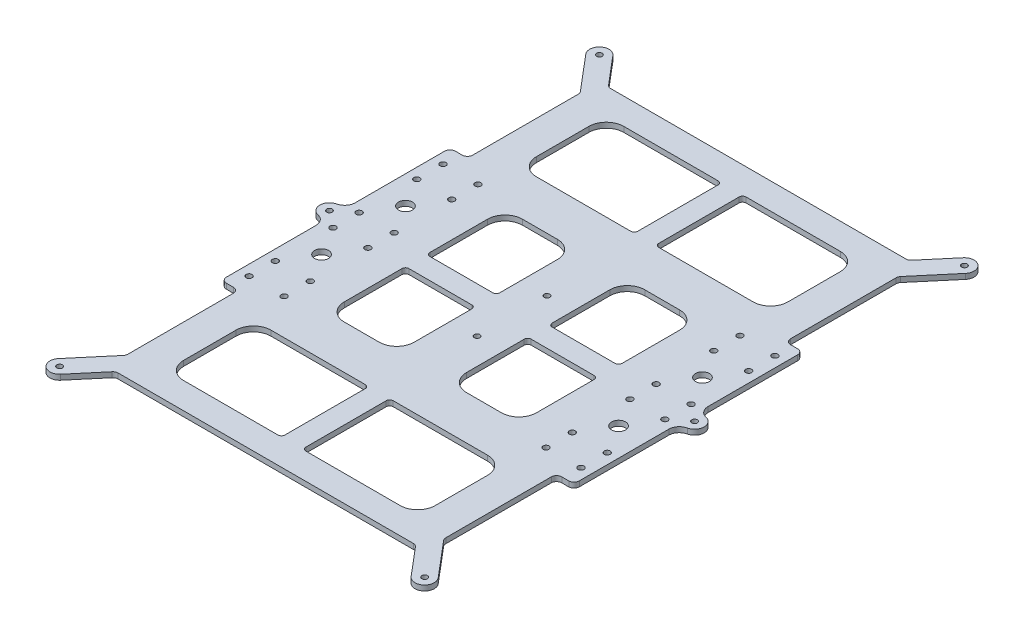
SolidWorks part; units mm, degrees
ref_plane "Alzado" through (0, 0, 0) normal (0, 0, 1) x (1, 0, 0)
ref_plane "Planta" through (0, 0, 0) normal (0, 1, 0) x (1, 0, 0)
ref_plane "Vista lateral" through (0, 0, 0) normal (1, 0, 0) x (0, 0, -1)
sketch "Croquis1" plane through (0, 0, 0) normal (0, 1, 0) x (1, 0, 0)
  line L0 (110, 320) -> (110, 0) construction
  line L1 (0, 0) -> (220, 0)
  line L2 (0, 0) -> (0, 320)
  line L3 (0, 320) -> (220, 320)
  line L4 (220, 0) -> (220, 320)
  line L5 (0, 160) -> (220, 160) construction
  line L6 (19, 320) -> (19, 0) construction
  line L7 (31, 320) -> (31, 0) construction
  line L8 (189, 320) -> (189, 0) construction
  line L9 (201, 320) -> (201, 0) construction
  line L10 (195, 320) -> (195, 0) construction
  line L11 (25, 320) -> (25, 0) construction
  line L12 (5.5, 314.5) -> (5.5, 160) construction
  circle A0 centre (185, 167.5) radius 1.7
  circle A1 centre (205, 167.5) radius 1.7
  circle A4 centre (185, 152.5) radius 1.7
  circle A5 centre (205, 152.5) radius 1.7
  circle A7 centre (35, 215.5) radius 1.7
  circle A8 centre (35, 200.5) radius 1.7
  circle A10 centre (35, 119.5) radius 1.7
  circle A13 centre (35, 104.5) radius 1.7
  circle A14 centre (5.5, 314.5) radius 1.6
  circle A15 centre (214.5, 314.5) radius 1.6
  circle A16 centre (214.5, 5.5) radius 1.6
  circle A17 centre (5.5, 5.5) radius 1.6
  circle A18 centre (15, 200.5) radius 1.7
  circle A19 centre (15, 215.5) radius 1.7
  circle A20 centre (15, 104.5) radius 1.7
  circle A21 centre (15, 119.5) radius 1.7
  circle A22 centre (110, 180) radius 1.6
  circle A23 centre (110, 140) radius 1.6
  circle A24 centre (185, 104.5) radius 1.7
  circle A25 centre (205, 104.5) radius 1.7
  circle A26 centre (205, 119.5) radius 1.7
  circle A27 centre (185, 119.5) radius 1.7
  circle A28 centre (185, 200.5) radius 1.7
  circle A29 centre (185, 215.5) radius 1.7
  circle A30 centre (205, 200.5) radius 1.7
  circle A31 centre (205, 215.5) radius 1.7
  circle A32 centre (5.5, 160) radius 1.6
  circle A33 centre (35, 152.5) radius 1.7
  circle A34 centre (15, 152.5) radius 1.7
  circle A35 centre (15, 167.5) radius 1.7
  circle A36 centre (35, 167.5) radius 1.7
  circle A37 centre (214.5, 160) radius 1.6
  circle A38 centre (25, 136) radius 4
  circle A39 centre (25, 184) radius 4
  circle A40 centre (195, 136) radius 4
  circle A41 centre (195, 184) radius 4
  dimension "D8" = 3.4
  dimension "D13" = 6
  dimension "D14" = 3.4
  dimension "D17" = 3.2
  dimension "D23" = 3.2
  dimension "D18" = 20
  dimension "D19" = 8
  dimension "D1" = 320
  dimension "D2" = 220
  dimension "D3" = 12
  dimension "D4" = 12
  dimension "D5" = 158
  dimension "D6" = 19
  dimension "D7" = 6
  dimension "D9" = 20
  dimension "D10" = 10
  dimension "D11" = 7.5
  dimension "D12" = 7.5
  dimension "D15" = 10
  dimension "D16" = 15
  dimension "D20" = 10
  dimension "D21" = 104.5
  dimension "D22" = 16.5
  dimension "D24" = 5.5
  dimension "D25" = 5.5
extrude "Saliente-Extruir1" add sketch "Croquis1" along normal blind 3
sketch "Croquis2" plane through (0, 3, 0) normal (0, 1, 0) x (1, 0, 0)
  line L0 (220, 160) -> (0, 160) construction
  line L2 (9, 9) -> (211, 9) construction
  line L3 (220, 0) -> (220, 320) construction
  line L4 (9, 148.775) -> (9, 94.5)
  line L5 (110, 320) -> (110, 0) construction
  line L6 (220, 320) -> (0, 320) construction
  line L7 (0, 0) -> (220, 0) construction
  line L8 (9, 9) -> (211, 9)
  line L9 (211, 9) -> (211, 311)
  line L10 (211, 311) -> (9, 311)
  line L11 (9, 311) -> (9, 9)
  line L15 (9, 225.5) -> (9, 171.225)
  line L16 (9, 225.5) -> (19, 225.5)
  line L18 (19, 94.5) -> (9, 94.5)
  line L19 (19, 94.5) -> (19, 30)
  line L20 (24.1066, 19) -> (195.8934, 19)
  line L21 (210.2988, 1.9504) -> (195.8934, 19)
  line L22 (1.2988, 9.0496) -> (19, 30)
  line L23 (9.7012, 1.9504) -> (24.1066, 19)
  line L24 (9, 148.775) -> (9, 9) construction
  line L25 (19, 148.775) -> (19, 19) construction
  line L26 (19, 19) -> (201, 19) construction
  line L27 (211, 9) -> (211, 311) construction
  line L28 (19, 225.5) -> (19, 290)
  line L29 (24.1066, 301) -> (195.8934, 301)
  line L30 (1.2988, 310.9504) -> (19, 290)
  line L31 (9.7012, 318.0496) -> (24.1066, 301)
  line L32 (0, 320) -> (0, 0) construction
  line L33 (218.7012, 9.0496) -> (201, 30)
  line L34 (201, 19) -> (201, 311) construction
  line L35 (201, 94.5) -> (201, 30)
  line L36 (201, 94.5) -> (211, 94.5)
  line L37 (211, 148.775) -> (211, 94.5)
  line L38 (211, 225.5) -> (211, 171.225)
  line L39 (211, 225.5) -> (201, 225.5)
  line L40 (201, 225.5) -> (201, 290)
  line L41 (218.7012, 310.9504) -> (201, 290)
  line L42 (210.2988, 318.0496) -> (195.8934, 301)
  line L43 (182, 276) -> (182, 246)
  line L44 (102, 286) -> (48, 286)
  line L46 (102, 236) -> (48, 236)
  line L47 (38, 276) -> (38, 246)
  line L48 (118, 236) -> (172, 236)
  line L52 (104, 284) -> (104, 238)
  line L53 (116, 284) -> (116, 238)
  line L54 (118, 286) -> (172, 286)
  line L55 (102, 84) -> (48, 84)
  line L56 (38, 44) -> (38, 74)
  line L57 (102, 34) -> (48, 34)
  line L58 (104, 36) -> (104, 82)
  line L59 (116, 36) -> (116, 82)
  line L60 (118, 34) -> (172, 34)
  line L61 (182, 44) -> (182, 74)
  line L62 (118, 84) -> (172, 84)
  line L63 (55, 152) -> (55, 119)
  line L64 (93, 166) -> (57, 166)
  line L65 (95, 168) -> (95, 201)
  line L66 (85, 211) -> (65, 211)
  line L67 (55, 168) -> (55, 201)
  line L68 (85, 109) -> (65, 109)
  line L69 (95, 152) -> (95, 119)
  line L70 (93, 154) -> (57, 154)
  line L71 (135, 109) -> (155, 109)
  line L72 (165, 152) -> (165, 119)
  line L73 (125, 152) -> (125, 119)
  line L74 (127, 154) -> (163, 154)
  line L75 (127, 166) -> (163, 166)
  line L76 (165, 168) -> (165, 201)
  line L77 (135, 211) -> (155, 211)
  line L78 (125, 168) -> (125, 201)
  arc A2 (1.2988, 9.0496) -> (9.7012, 1.9504) centre (5.5, 5.5) ccw
  arc A3 (4.3043, 165.3685) -> (4.3043, 154.6315) centre (5.5, 160) ccw
  arc A4 (9, 148.775) -> (4.3043, 154.6315) centre (3, 148.775) ccw
  arc A5 (9, 171.225) -> (4.3043, 165.3685) centre (3, 171.225) cw
  circle A6 centre (35, 215.5) radius 1.7 construction
  circle A7 centre (35, 104.5) radius 1.7 construction
  arc A8 (48, 236) -> (38, 246) centre (48, 246) cw
  arc A10 (1.2988, 310.9504) -> (9.7012, 318.0496) centre (5.5, 314.5) cw
  arc A11 (218.7012, 9.0496) -> (210.2988, 1.9504) centre (214.5, 5.5) cw
  arc A12 (211, 148.775) -> (215.6957, 154.6315) centre (217, 148.775) cw
  arc A13 (215.6957, 165.3685) -> (215.6957, 154.6315) centre (214.5, 160) cw
  arc A14 (211, 171.225) -> (215.6957, 165.3685) centre (217, 171.225) ccw
  arc A15 (218.7012, 310.9504) -> (210.2988, 318.0496) centre (214.5, 314.5) ccw
  arc A16 (48, 286) -> (38, 276) centre (48, 276) ccw
  arc A17 (172, 236) -> (182, 246) centre (172, 246) ccw
  arc A18 (172, 286) -> (182, 276) centre (172, 276) cw
  arc A19 (48, 84) -> (38, 74) centre (48, 74) ccw
  arc A20 (48, 34) -> (38, 44) centre (48, 44) cw
  arc A21 (172, 34) -> (182, 44) centre (172, 44) ccw
  arc A22 (172, 84) -> (182, 74) centre (172, 74) cw
  arc A23 (102, 236) -> (104, 238) centre (102, 238) ccw
  arc A24 (102, 286) -> (104, 284) centre (102, 284) cw
  arc A25 (116, 284) -> (118, 286) centre (118, 284) cw
  arc A26 (118, 236) -> (116, 238) centre (118, 238) cw
  arc A27 (116, 82) -> (118, 84) centre (118, 82) cw
  arc A28 (116, 36) -> (118, 34) centre (118, 36) ccw
  arc A29 (102, 34) -> (104, 36) centre (102, 36) ccw
  arc A30 (102, 84) -> (104, 82) centre (102, 82) cw
  arc A31 (95, 201) -> (85, 211) centre (85, 201) ccw
  arc A32 (65, 211) -> (55, 201) centre (65, 201) ccw
  arc A33 (65, 109) -> (55, 119) centre (65, 119) cw
  arc A34 (95, 119) -> (85, 109) centre (85, 119) cw
  arc A35 (155, 109) -> (165, 119) centre (155, 119) ccw
  arc A36 (125, 119) -> (135, 109) centre (135, 119) ccw
  arc A37 (155, 211) -> (165, 201) centre (155, 201) cw
  arc A38 (125, 201) -> (135, 211) centre (135, 201) cw
  arc A39 (127, 166) -> (125, 168) centre (127, 168) cw
  arc A40 (163, 166) -> (165, 168) centre (163, 168) ccw
  arc A41 (165, 152) -> (163, 154) centre (163, 152) ccw
  arc A42 (125, 152) -> (127, 154) centre (127, 152) cw
  arc A43 (55, 152) -> (57, 154) centre (57, 152) cw
  arc A44 (95, 152) -> (93, 154) centre (93, 152) ccw
  arc A45 (93, 166) -> (95, 168) centre (93, 168) ccw
  arc A46 (57, 166) -> (55, 168) centre (57, 168) cw
  point P28 (110, 19)
  point P71 (110, 301)
  point P76 (38, 236)
  point P79 (38, 286)
  point P106 (104, 236)
  point P109 (104, 286)
  point P112 (116, 286)
  point P115 (116, 236)
  point P118 (116, 84)
  point P121 (116, 34)
  point P124 (104, 34)
  point P127 (104, 84)
  point P137 (95, 211)
  point P140 (55, 211)
  point P167 (125, 166)
  point P170 (165, 166)
  point P173 (165, 154)
  point P176 (125, 154)
  point P179 (55, 154)
  point P182 (95, 154)
  point P185 (95, 166)
  point P188 (55, 166)
  dimension "D2" = 11
  dimension "D3" = 11
  dimension "D4" = 6
  dimension "D5" = 10
  dimension "D6" = 10
  dimension "D7" = 50
  dimension "D12" = 10
  dimension "D14" = 2
  dimension "D19" = 10
  dimension "D20" = 2
  dimension "D9" = 30
  dimension "D10" = 15
  dimension "D8" = 19
  dimension "D11" = 38
  dimension "D13" = 6
  dimension "D15" = 6
  dimension "D16" = 15
  dimension "D17" = 40
  dimension "D18" = 45
  dimension "D1" = 9
extrude "Cortar-Extruir1" cut sketch "Croquis2" against normal up to surface (3 mm away) flip side to cut up to face at (195, 0, -140)
fillet "Redondeo1" radius 3 16 edges at (211, 1.5, -225.5) (211, 1.5, -94.5) (9, 1.5, -225.5) (9, 1.5, -94.5) (24.1066, 1.5, -301) (195.8934, 1.5, -301) (201, 1.5, -290) (201, 1.5, -225.5) (201, 1.5, -94.5) (201, 1.5, -30) (195.8934, 1.5, -19) (24.1066, 1.5, -19) (19, 1.5, -30) (19, 1.5, -94.5) (19, 1.5, -290) (19, 1.5, -225.5)
